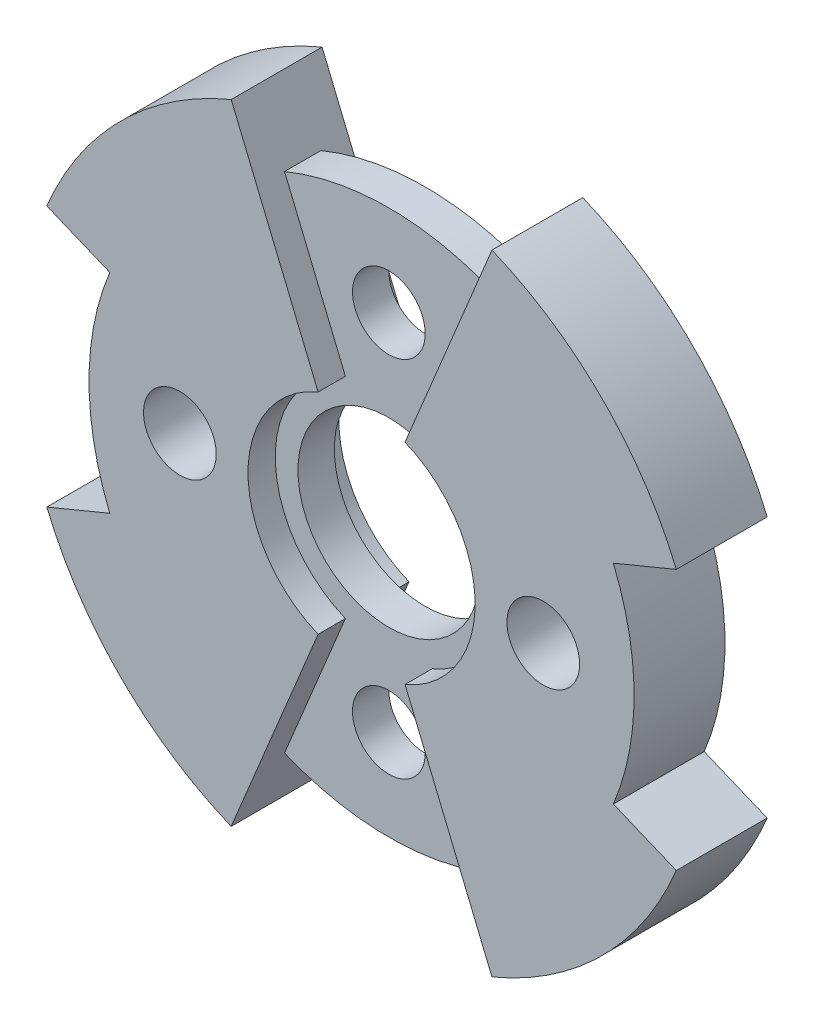
SolidWorks part; units mm, degrees
ref_plane "Front Plane" through (0, 0, 0) normal (0, 0, 1) x (1, 0, 0)
ref_plane "Top Plane" through (0, 0, 0) normal (0, 1, 0) x (1, 0, 0)
ref_plane "Right Plane" through (0, 0, 0) normal (1, 0, 0) x (0, 0, -1)
sketch "Sketch1" plane through (0, 0, 0) normal (0, 0, 1) x (1, 0, 0)
  line L0 (0, 0) -> (50000, 0) construction
  line L1 (0, 0) -> (0, 50000) construction
  line L2 (0, 0) -> (31.6259, 76.3517)
  line L3 (0, 0) -> (78.1652, 32.3771)
  line L4 (0, 0) -> (78.1652, -32.3771)
  line L5 (0, 0) -> (-31.6259, 76.3517)
  line L6 (0, 0) -> (-78.1652, -32.3771)
  line L7 (0, 0) -> (-78.1652, 32.3771)
  line L8 (0, 0) -> (31.6259, -76.3517)
  line L9 (0, 0) -> (-31.6259, -76.3517)
  circle A0 centre (0, 0) radius 20
  circle A1 centre (0, 0) radius 75
  circle A2 centre (0, 0) radius 60
  circle A3 centre (0, 0) radius 40 construction
  circle A4 centre (0, 0) radius 25
  circle A6 centre (0, 40) radius 8
  circle A7 centre (40, 0) radius 8
  circle A8 centre (0, -40) radius 8
  circle A9 centre (-40, 0) radius 8
  point P23 (0, 0)
  point P29 (0, 0)
  dimension "D1" = 40
  dimension "D2" = 150
  dimension "D3" = 120
  dimension "D4" = 80
  dimension "D5" = 50
  dimension "D8" = 16
  dimension "D6" = 45
  dimension "D7" = 45
  dimension "D9" = 4
extrude "Boss-Extrude1" add sketch "Sketch1" along normal mid plane 20 contours A2 L3 A1 L2 | A4 L3 A2 L2 | A4 L8 A2 L4 | A4 L4 A2 L3 A7 | A2 L8 A1 L4 | A2 L5 A1 L7 | A4 L5 A2 L7 | A4 L7 A2 L6 A9 | A2 L6 A1 L9 | A4 L6 A2 L9 region at (30.9407, 30.9407, 0) region at (39.4903, 15.7198, 0) region at (30.9407, -30.9407, 0) region at (-30.9407, 30.9407, 0) region at (-30.9407, -30.9407, 0) region at (-39.4903, -15.7198, 0) region at (46.7038, 46.7038, 0) region at (46.7038, -46.7038, 0) region at (-46.7038, 46.7038, 0) region at (-46.7038, -46.7038, 0)
extrude "Boss-Extrude2" add sketch "Sketch1<3>" along normal mid plane 8 contours A4 L2 A2 L5 A6 | A4 L9 A2 L8 A8 | L7 A4 L6 A0 | L6 A4 L9 A0 | L9 A4 L8 A0 | L8 A4 L4 A0 | L4 A4 L3 A0 | L3 A4 L2 A0 | L2 A4 L5 A0 | L5 A4 L7 A0 region at (0, 22.0164, 0) region at (15.5679, 15.5679, 0) region at (22.0164, 0, 0) region at (15.5679, -15.5679, 0) region at (-15.5679, 15.5679, 0) region at (-15.5679, -15.5679, 0) region at (-22.0164, 0, 0) region at (0, -22.0164, 0) region at (0, 25.5891, 0) region at (15.7198, -39.4903, 0)
sketch "Sketch1<3>" plane through (0, 0, 0) normal (0, 0, 1) x (1, 0, 0) same geometry as "Sketch1"
